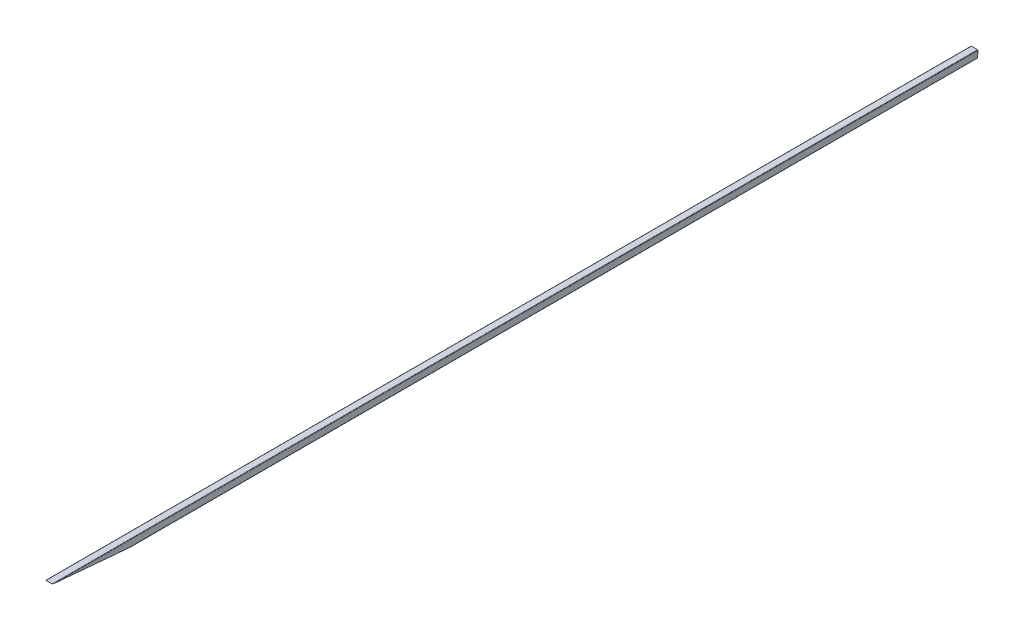
SolidWorks part; units mm, degrees
material "ASTM A500 Grade B"
ref_plane "Front Plane" through (0, 0, 0) normal (0, 0, 1) x (1, 0, 0)
ref_plane "Top Plane" through (0, 0, 0) normal (0, 1, 0) x (1, 0, 0)
ref_plane "Right Plane" through (0, 0, 0) normal (1, 0, 0) x (0, 0, -1)
sketch "Sketch1" plane through (0, 0, 0) normal (0, 0, 1) x (1, 0, 0)
  line L0 (5.3086, -2.7686) -> (32.7914, -2.7686)
  line L1 (2.54, 0) -> (35.56, 0)
  line L2 (0, -2.54) -> (0, -35.56)
  line L3 (2.54, -38.1) -> (35.56, -38.1)
  line L4 (38.1, -2.54) -> (38.1, -35.56)
  line L5 (35.3314, -5.3086) -> (35.3314, -32.7914)
  line L6 (5.3086, -35.3314) -> (32.7914, -35.3314)
  line L7 (2.7686, -5.3086) -> (2.7686, -32.7914)
  line L8 (0, 0) -> (0, -38.1) construction
  line L9 (0, -38.1) -> (38.1, -38.1) construction
  line L10 (38.1, 0) -> (38.1, -38.1) construction
  line L11 (2.7686, -2.7686) -> (2.7686, -35.3314) construction
  line L12 (2.7686, -35.3314) -> (35.3314, -35.3314) construction
  line L13 (35.3314, -2.7686) -> (35.3314, -35.3314) construction
  line L14 (2.7686, -2.7686) -> (35.3314, -2.7686) construction
  line L15 (0, 0) -> (38.1, 0) construction
  arc A0 (0, -35.56) -> (2.54, -38.1) centre (2.54, -35.56) ccw
  arc A1 (38.1, -35.56) -> (35.56, -38.1) centre (35.56, -35.56) cw
  arc A2 (2.7686, -32.7914) -> (5.3086, -35.3314) centre (5.3086, -32.7914) ccw
  arc A3 (32.7914, -35.3314) -> (35.3314, -32.7914) centre (32.7914, -32.7914) ccw
  arc A4 (35.3314, -5.3086) -> (32.7914, -2.7686) centre (32.7914, -5.3086) ccw
  arc A5 (38.1, -2.54) -> (35.56, 0) centre (35.56, -2.54) ccw
  arc A6 (0, -2.54) -> (2.54, 0) centre (2.54, -2.54) cw
  arc A7 (5.3086, -2.7686) -> (2.7686, -5.3086) centre (5.3086, -5.3086) ccw
  point P12 (0, -38.1)
  dimension "D4" = 2.54
  dimension "D3" = 2.7686
extrude "Boss-Extrude1" add sketch "Sketch1" along normal blind 5000
sketch "Sketch2" plane through (38.1, 0, 0) normal (1, 0, 0) x (0, 0, -1)
  line L0 (-5000, 0) -> (-4564.515, -38.1)
  line L1 (-5000, -38.1) -> (0, -38.1) construction
  line L2 (-5000, 0) -> (0, 0) construction
  line L3 (-4564.515, -38.1) -> (-5000, -38.1)
  line L4 (-5000, -38.1) -> (-5000, 0)
  dimension "D1" = 5
extrude "Cut-Extrude1" cut sketch "Sketch2" against normal through all
sketch "Sketch4" plane through (38.1, 0, 0) normal (1, 0, 0) x (0, 0, -1)
  line L0 (0, 0) -> (-3.3333, -38.1)
  line L1 (-4564.515, -38.1) -> (0, -38.1) construction
  line L2 (0, -35.56) -> (0, -2.54) construction
  line L3 (-3.3333, -38.1) -> (0, -38.1)
  line L4 (0, -38.1) -> (0, 0)
  dimension "D1" = 5
extrude "Cut-Extrude2" cut sketch "Sketch4" against normal through all
fillet "Fillet1" [suppressed] radius 1
fillet "Fillet2" [suppressed] radius 1
fillet "Fillet3" [suppressed] radius 0.5
